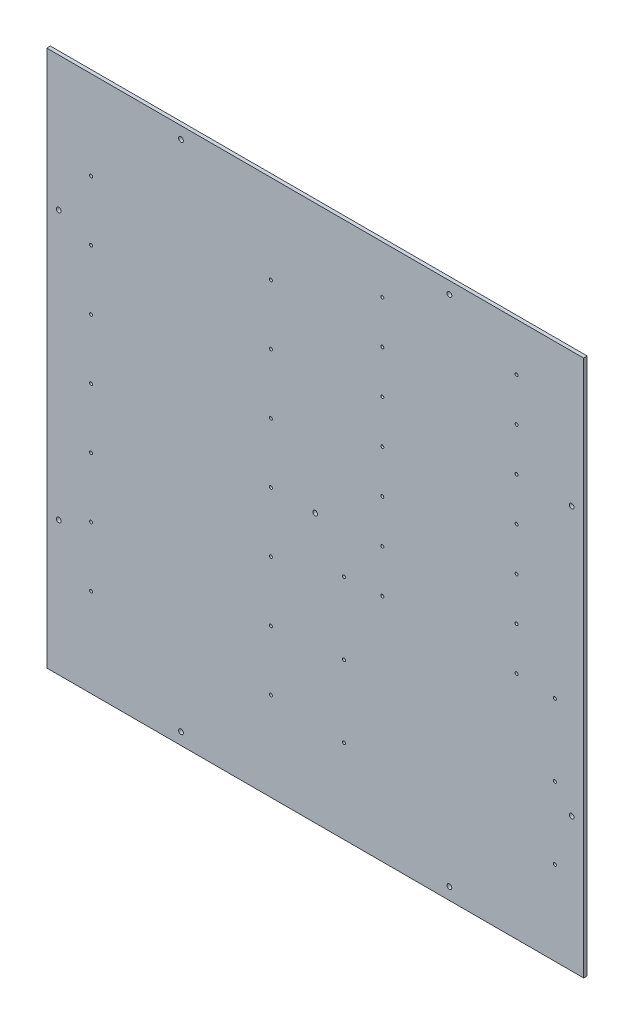
SolidWorks part; units mm, degrees
material "6061-T6 (SS)"
ref_plane "Piano frontale" through (0, 0, 0) normal (0, 0, 1) x (1, 0, 0)
ref_plane "Piano superiore" through (0, 0, 0) normal (0, 1, 0) x (1, 0, 0)
ref_plane "Piano destro" through (0, 0, 0) normal (1, 0, 0) x (0, 0, -1)
sketch "Schizzo1" plane through (0, 0, 0) normal (0, 0, 1) x (1, 0, 0)
  line L0 (10, 448) -> (10, -28.2593) construction
  line L1 (0, 0) -> (448, 0)
  line L2 (0, 0) -> (0, 448)
  line L3 (0, 448) -> (448, 448)
  line L4 (448, 0) -> (448, 448)
  line L6 (224, 448) -> (224, 0) construction
  line L7 (438, 448) -> (438, -28.2593) construction
  line L8 (0, 438) -> (525.0128, 438) construction
  line L9 (0, 10) -> (525.0128, 10) construction
  line L10 (0, 448) -> (0, 224) construction
  line L11 (0, 448) -> (0, 224) construction
  line L15 (0, 336) -> (224, 336) construction
  line L25 (112, 448) -> (112, 224) construction
  line L45 (248, -38.4576) -> (248, 190) construction
  line L47 (424, -38.4576) -> (424, 190) construction
  line L58 (336, 27.7675) -> (336, 161.4481) construction
  line L59 (112, 398) -> (112, 174) construction
  line L60 (112, 348) -> (112, 124) construction
  line L61 (112, 298) -> (112, 74) construction
  circle A0 centre (10, 336) radius 2
  circle A1 centre (336, 438) radius 2
  circle A2 centre (438, 336) radius 2
  circle A3 centre (438, 112) radius 2
  circle A4 centre (336, 10) radius 2
  circle A5 centre (112, 10) radius 2
  circle A6 centre (10, 112) radius 2
  circle A7 centre (36.9588, 224) radius 1.25
  circle A8 centre (112, 438) radius 2
  circle A9 centre (36.9588, 274) radius 1.25
  circle A10 centre (187.0412, 274) radius 1.25
  circle A11 centre (36.9588, 324) radius 1.25
  circle A12 centre (187.0412, 324) radius 1.25
  circle A13 centre (36.9588, 374) radius 1.25
  circle A14 centre (187.0412, 374) radius 1.25
  circle A15 centre (36.9588, 174) radius 1.25
  circle A16 centre (248, 70) radius 1.25
  circle A17 centre (248, 130) radius 1.25
  circle A18 centre (424, 130) radius 1.25
  circle A19 centre (424, 70) radius 1.25
  circle A20 centre (187.0412, 174) radius 1.25
  circle A21 centre (280, 408) radius 1.25
  circle A22 centre (392, 408) radius 1.25
  circle A23 centre (36.9588, 124) radius 1.25
  circle A24 centre (187.0412, 124) radius 1.25
  circle A25 centre (280, 372) radius 1.25
  circle A26 centre (392, 372) radius 1.25
  circle A27 centre (36.9588, 74) radius 1.25
  circle A28 centre (187.0412, 74) radius 1.25
  circle A29 centre (280, 336) radius 1.25
  circle A30 centre (392, 336) radius 1.25
  circle A33 centre (280, 300) radius 1.25
  circle A34 centre (392, 300) radius 1.25
  circle A37 centre (280, 264) radius 1.25
  circle A38 centre (392, 264) radius 1.25
  circle A41 centre (280, 228) radius 1.25
  circle A42 centre (392, 228) radius 1.25
  circle A45 centre (280, 192) radius 1.25
  circle A46 centre (392, 192) radius 1.25
  circle A69 centre (187.0412, 224) radius 1.25
  circle A70 centre (224, 224) radius 2
  circle A71 centre (424, 190) radius 1.25
  circle A72 centre (248, 190) radius 1.25
  point P33 (36.9588, 224)
  point P36 (36.9588, 174)
  point P37 (36.9588, 274)
  point P42 (36.9588, 324)
  point P49 (112, 438)
  point P53 (36.9588, 374)
  point P64 (36.9588, 124)
  point P71 (36.9588, 74)
  point P82 (253.9707, 256)
  point P89 (253.9707, 224)
  point P96 (253.9707, 192)
  point P103 (253.9707, 384)
  point P110 (253.9707, 352)
  point P117 (253.9707, 320)
  point P141 (253.9707, 288)
  point P148 (253.9707, 160)
  point P155 (253.9707, 128)
  point P162 (253.9707, 96)
  point P169 (253.9707, 64)
  point P179 (280.1758, 232.4048)
  point P193 (280.1085, 282.4047)
  point P207 (280.0413, 332.4047)
  dimension "D5" = 30
  dimension "D18" = 7
  dimension "D16" = 2.5
  dimension "D9" = 4
  dimension "D10" = 4
  dimension "D20" = 4
  dimension "D1" = 448
  dimension "D2" = 448
  dimension "D3" = 10
  dimension "D4" = 10
  dimension "D6" = 4
  dimension "D7" = 112
  dimension "D8" = 112
  dimension "D15" = 88
extrude "Estrusione-Estrusione1" add sketch "Schizzo1" against normal blind 3
